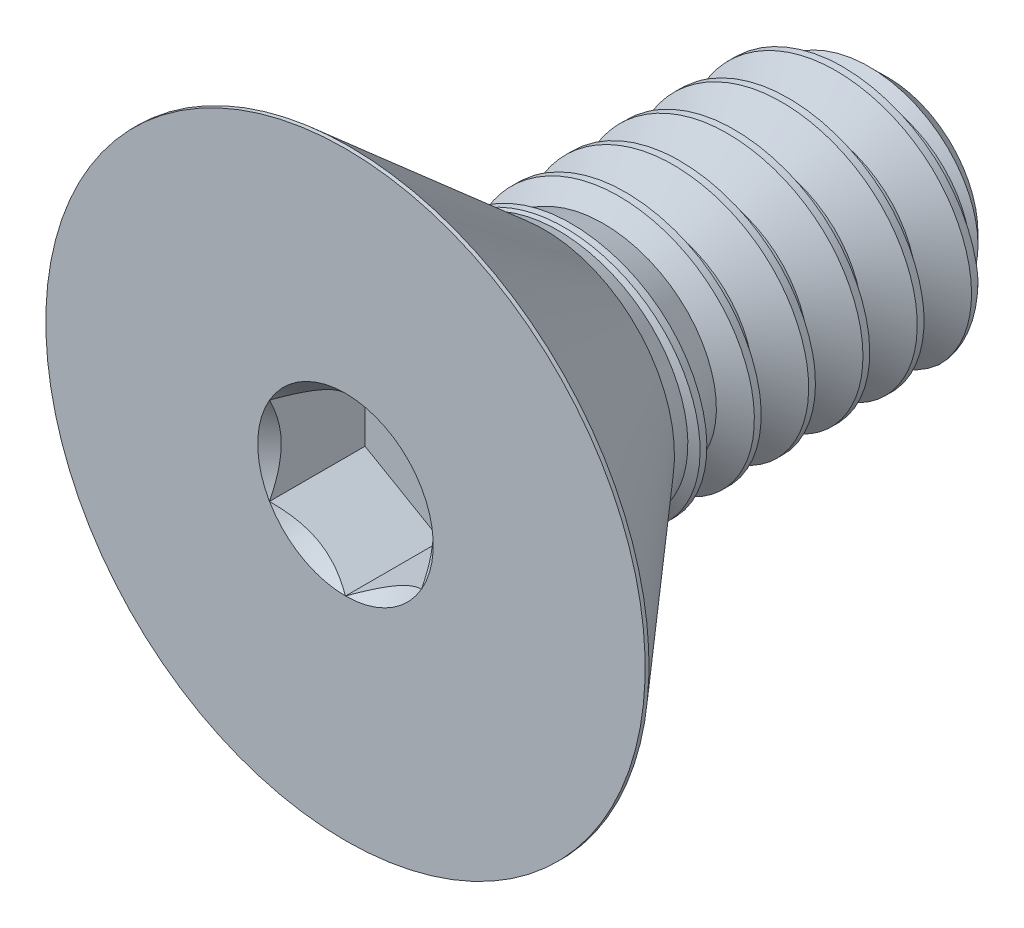
SolidWorks part; units mm, degrees
ref_plane "Front Plane" through (0, 0, 0) normal (0, 0, 1) x (1, 0, 0)
ref_plane "Top Plane" through (0, 0, 0) normal (0, 1, 0) x (1, 0, 0)
ref_plane "Right Plane" through (0, 0, 0) normal (1, 0, 0) x (0, 0, -1)
sketch "Sketch1" plane through (0, 0, 0) normal (1, 0, 0) x (0, 0, -1)
  line L0 (-1.5875, 0) -> (1.5875, 0) construction
  line L1 (-1.5875, 0) -> (-1.5875, 1.7526)
  line L2 (-1.5875, 1.7526) -> (-1.5651, 1.7526)
  line L3 (-1.5651, 1.7526) -> (-0.4699, 0.8005)
  line L4 (-1.5651, -1.7526) -> (-0.4699, -0.8005)
  line L5 (1.5875, 0) -> (1.5875, 0.762)
  line L6 (1.5875, 0.762) -> (-0.4699, 0.762)
  line L7 (1.3494, 0.762) -> (1.5875, 0.5239)
  line L8 (1.5677, 0.7964) -> (1.7264, 0.5214) construction
  line L9 (1.7264, 0.5214) -> (1.8852, 0.7964) construction
  line L10 (1.8852, 0.7964) -> (1.5677, 0.7964) construction
  line L11 (1.5776, 0.7792) -> (1.8752, 0.7792)
  line L12 (1.8752, 0.7792) -> (1.7462, 0.5558)
  line L13 (1.7462, 0.5558) -> (1.7066, 0.5558)
  line L14 (1.7066, 0.5558) -> (1.5776, 0.7792)
  line L15 (1.7264, 0.5558) -> (1.7264, 0.5214) construction
  line L16 (1.5875, 0.762) -> (1.8653, 0.762) construction
  line L17 (1.7264, 0.7964) -> (1.7264, 0.762) construction
  line L18 (1.5875, -0.762) -> (-0.4699, -0.762)
  arc A0 (-0.4699, 0.8005) -> (-0.3669, 0.762) centre (-0.3669, 0.919) ccw
  point P2 (0, 0)
  point P23 (-1.0287, 0)
  point P27 (1.7264, 0.7792)
  point P30 (1.1113, -0.762)
  point P31 (-0.4699, 1.7526)
  point P34 (-1.5651, -1.7526)
  dimension "Length" = 3.175
  dimension "Head Height" = 1.1176
  dimension "Head Diameter" = 3.5052
  dimension "Countersink Angle" = 82
  dimension "Screw Size Decimal Equivalent" = 1.524
  dimension "Pitch" = 0.3175
  dimension "D4" = 0.0397
  dimension "D3" = 45
  dimension "D5" = 0.2381
  dimension "D6" = 0.5588
  dimension "D1" = 0.4763
  dimension "D7" = 0.0224
sketch "Sketch8" plane through (0, 0, 0) normal (0, 0, 1) x (1, 0, 0)
  line L1 (0, 0.5133) -> (-0.4445, 0.2566)
  line L2 (-0.4445, 0.2566) -> (-0.4445, -0.2566)
  line L3 (-0.4445, -0.2566) -> (0, -0.5133)
  line L4 (0, -0.5133) -> (0.4445, -0.2566)
  line L5 (0.4445, -0.2566) -> (0.4445, 0.2566)
  line L6 (0.4445, 0.2566) -> (0, 0.5133)
  circle A0 centre (0, 0) radius 0.4445 construction
  dimension "Drive Size" = 0.889
sketch "Sketch2" plane through (0, 0, 0) normal (1, 0, 0) x (0, 0, -1)
  line L0 (-1.5651, 1.7526) -> (-0.4699, 0.8005) construction
  line L1 (-1.5875, 0) -> (-1.5875, 1.7526) construction
  line L2 (-1.5651, 1.7526) -> (-0.4256, 0.762)
  line L3 (-1.5875, 0) -> (-1.5875, 1.7526)
  line L4 (-1.5875, 1.7526) -> (-1.5651, 1.7526) construction
  line L5 (-1.5875, 1.7526) -> (-1.5651, 1.7526)
  line L6 (-0.4256, 0.762) -> (1.3494, 0.762)
  line L7 (1.3494, 0.762) -> (1.5875, 0.5239)
  line L8 (1.5875, 0.5239) -> (1.5875, 0)
  line L9 (1.5875, 0) -> (-1.5875, 0)
revolve "Revolve1" add sketch "Sketch2" angle 360 about L9
sketch "Sketch9" plane through (0, 0, 1.5875) normal (0, 0, 1) x (1, 0, 0)
  line L0 (0.4445, -0.2566) -> (0.4445, 0.2566) construction
  line L1 (0, -0.5133) -> (0.4445, -0.2566) construction
  line L2 (-0.4445, -0.2566) -> (0, -0.5133) construction
  line L3 (-0.4445, 0.2566) -> (-0.4445, -0.2566) construction
  line L4 (0, 0.5133) -> (-0.4445, 0.2566) construction
  line L5 (0.4445, 0.2566) -> (0, 0.5133) construction
  line L6 (0.4445, -0.2566) -> (0.4445, 0.2566)
  line L7 (0, -0.5133) -> (0.4445, -0.2566)
  line L8 (-0.4445, -0.2566) -> (0, -0.5133)
  line L9 (-0.4445, 0.2566) -> (-0.4445, -0.2566)
  line L10 (0, 0.5133) -> (-0.4445, 0.2566)
  line L11 (0.4445, 0.2566) -> (0, 0.5133)
sketch "Sketch10" plane through (0, 0, 1.5875) normal (0, 0, 1) x (1, 0, 0)
  circle A0 centre (0, 0) radius 0.5133
extrude "Cut-Extrude2" cut sketch "Sketch10" against normal up to vertex (0.5588 mm away) draft 45 up to point (0, 0, 1.0287)
extrude "Cut-Extrude1" cut sketch "Sketch9" against normal up to vertex (0.5588 mm away) up to point (0, 0, 1.0287)
ref_plane "Plane1" through (0, 0, 0.4256) normal (0, 0, 1) x (1, 0, 0)
split "Split1" trim tools "Plane1" bodies to split 111 resulting bodies 105 106
sketch "Sketch3" plane through (0, 0, -1.5875) normal (0, 0, -1) x (-1, 0, 0)
  circle A0 centre (0, 0) radius 0.762 construction
  circle A1 centre (0, 0) radius 0.762
curve "Helix/Spiral1" pitch 0.3175 height 3.175 radius 0.762 centre (0, 0, -1.5875) axis (0, 0, 1) start towards (0, 1, 0)
sketch "Sketch4" plane through (0, 0, 0) normal (1, 0, 0) x (0, 0, -1)
  line L0 (1.5776, 0.7792) -> (1.8752, 0.7792) construction
  line L1 (1.7066, 0.5558) -> (1.5776, 0.7792) construction
  line L2 (1.7462, 0.5558) -> (1.7066, 0.5558) construction
  line L3 (1.8752, 0.7792) -> (1.7462, 0.5558) construction
  line L4 (1.5776, 0.7792) -> (1.8752, 0.7792)
  line L5 (1.7066, 0.5558) -> (1.5776, 0.7792)
  line L6 (1.7462, 0.5558) -> (1.7066, 0.5558)
  line L7 (1.8752, 0.7792) -> (1.7462, 0.5558)
sweep "Cut-Sweep1" cut profiles "Sketch4" path "Helix/Spiral1" align with end faces yes
sketch "Sketch7" plane through (0, 0, 0.4256) normal (0, 0, 1) x (1, 0, 0)
  circle A0 centre (0, 0) radius 0.762
extrude "Boss-Extrude2" add sketch "Sketch7" against normal up to next (2.0131 mm away) draft 20
equation "\"D4@Sketch1\" = \"Pitch@Sketch1\" / 8"
equation "\"D5@Sketch1\"=\"Pitch@Sketch1\"*0.75"
equation "\"D4@Helix/Spiral1\"=\"Pitch@Sketch1\""
equation "\"D3@Helix/Spiral1\"=\"Length@Sketch1\""
equation "\"D6@Sketch1\"=\"Head Height@Sketch1\"/2"
equation "\"D1@Sketch1\"=\"Pitch@Sketch1\"*1.5"
equation "\"D7@Sketch1\"=\"Head Height@Sketch1\"*0.02"
